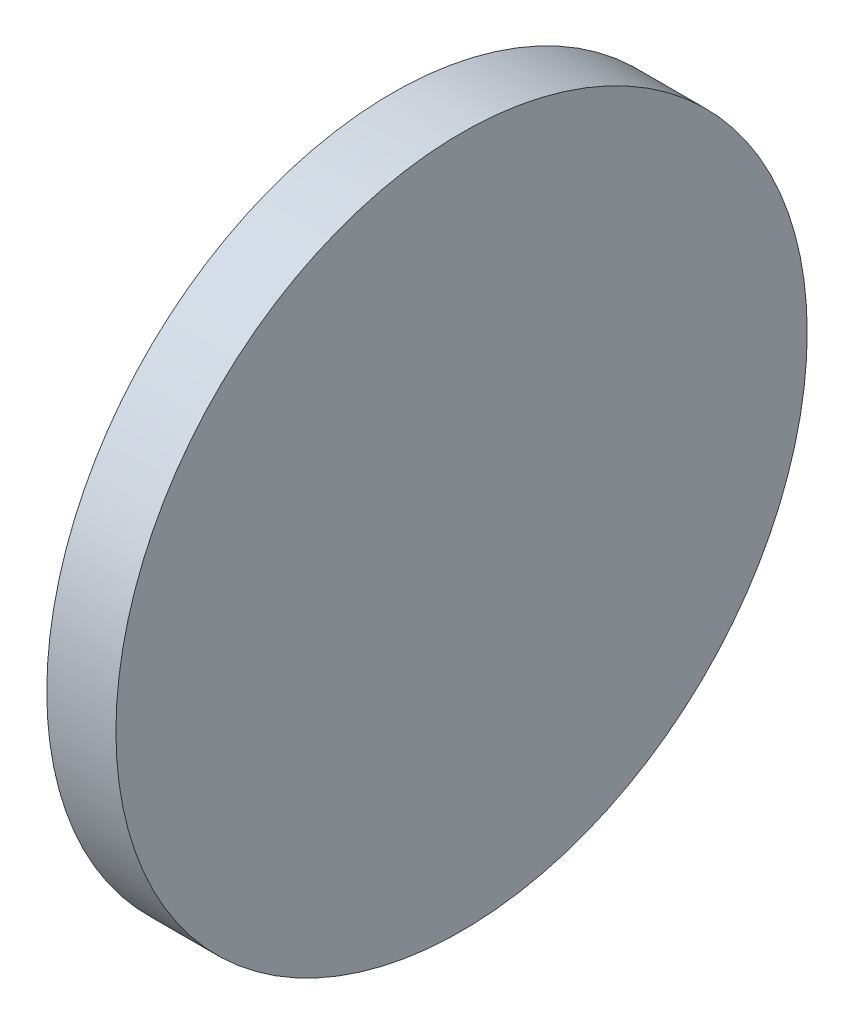
SolidWorks part; units mm, degrees
ref_plane "Front Plane" through (0, 0, 0) normal (0, 0, 1) x (1, 0, 0)
ref_plane "Top Plane" through (0, 0, 0) normal (0, 1, 0) x (1, 0, 0)
ref_plane "Right Plane" through (0, 0, 0) normal (1, 0, 0) x (0, 0, -1)
sketch "Sketch1" plane through (0, 0, 0) normal (1, 0, 0) x (0, 0, -1)
  circle A0 centre (0, 0) radius 100
  dimension "D1" = 200
extrude "Boss-Extrude1" add sketch "Sketch1" along normal blind 20
sketch "Sketch4" plane through (0, 0, 0) normal (-1, 0, 0) x (0, 0, 1)
  line L0 (0, 100) -> (0, -100) construction
  line L1 (-100, 0) -> (100, 0) construction
  line L2 (70.7107, 70.7107) -> (-70.7107, -70.7107) construction
  line L3 (-70.7107, 70.7107) -> (70.7107, -70.7107) construction
  circle A0 centre (0, 0) radius 65
  circle A1 centre (0, 0) radius 100 construction
  circle A2 centre (0, 65) radius 1.3
  circle A3 centre (45.9619, 45.9619) radius 1.3
  circle A4 centre (65, 0) radius 1.3
  circle A5 centre (45.9619, -45.9619) radius 1.3
  circle A6 centre (0, -65) radius 1.3
  circle A7 centre (-45.9619, -45.9619) radius 1.3
  circle A8 centre (-65, 0) radius 1.3
  circle A9 centre (-45.9619, 45.9619) radius 1.3
  point P16 (-45.9619, 45.9619)
  point P17 (45.9619, 45.9619)
  point P18 (-45.9619, -45.9619)
  point P19 (45.9619, -45.9619)
  point P34 (-47.9696, 43.8625)
  dimension "D1" = 130
  dimension "D3" = 2.6
  dimension "D2" = 45
extrude "Cut-Extrude2" cut sketch "Sketch4" against normal offset from surface (18 mm away) 2 contours A2 | A3 | A4 | A5 | A6 | A7 | A8 | A9 up to face at (20, 0, -100)
sketch "Sketch5" plane through (0, 0, 0) normal (-1, 0, 0) x (0, 0, 1)
  circle A0 centre (0, 65) radius 5
  circle A1 centre (-45.9619, 45.9619) radius 1.3 construction
  circle A2 centre (-65, 0) radius 1.3 construction
  circle A3 centre (-45.9619, -45.9619) radius 1.3 construction
  circle A4 centre (0, -65) radius 1.3 construction
  circle A5 centre (45.9619, -45.9619) radius 1.3 construction
  circle A6 centre (65, 0) radius 1.3 construction
  circle A7 centre (45.9619, 45.9619) radius 1.3 construction
  circle A8 centre (0, 65) radius 1.3 construction
  circle A9 centre (-45.9619, 45.9619) radius 1.3
  circle A10 centre (-65, 0) radius 1.3
  circle A11 centre (-45.9619, -45.9619) radius 1.3
  circle A12 centre (0, -65) radius 1.3
  circle A13 centre (45.9619, -45.9619) radius 1.3
  circle A14 centre (65, 0) radius 1.3
  circle A15 centre (45.9619, 45.9619) radius 1.3
  circle A16 centre (0, 65) radius 1.3
  circle A17 centre (45.9619, 45.9619) radius 5
  circle A18 centre (65, 0) radius 5
  circle A19 centre (45.9619, -45.9619) radius 5
  circle A20 centre (0, -65) radius 5
  circle A21 centre (-45.9619, -45.9619) radius 5
  circle A22 centre (-65, 0) radius 5
  circle A23 centre (-45.9619, 45.9619) radius 5
  dimension "D1" = 10
extrude "Boss-Extrude3" add sketch "Sketch5" along normal blind 10
